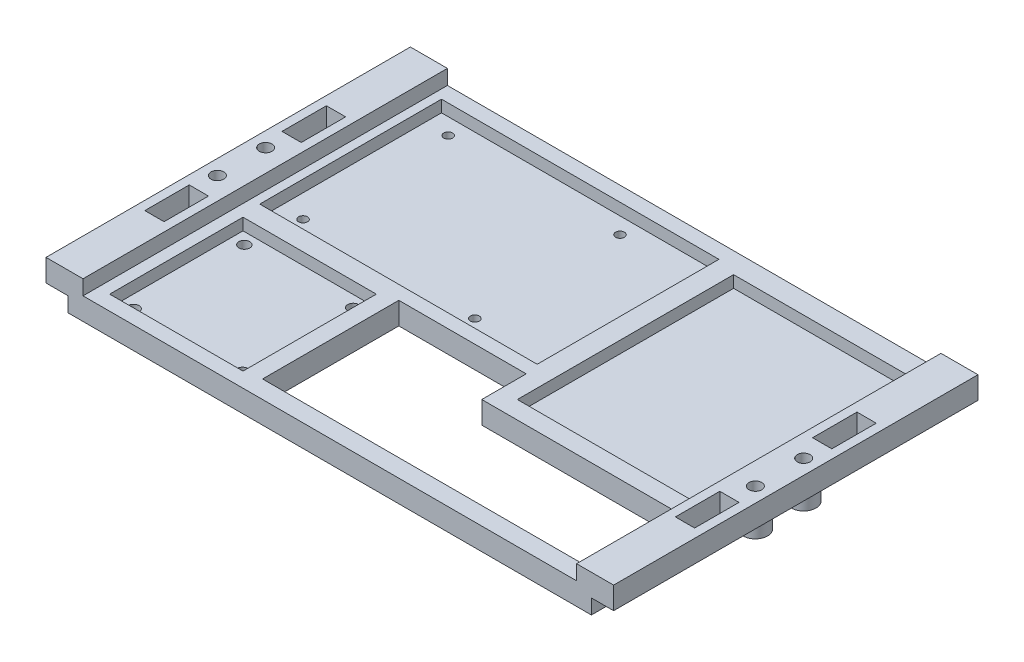
SolidWorks part; units mm, degrees
ref_plane "Front Plane" through (0, 0, 0) normal (0, 0, 1) x (1, 0, 0)
ref_plane "Top Plane" through (0, 0, 0) normal (0, 1, 0) x (1, 0, 0)
ref_plane "Right Plane" through (0, 0, 0) normal (1, 0, 0) x (0, 0, -1)
sketch "Sketch2" plane through (0, 0, 0) normal (0, 0, 1) x (1, 0, 0)
  line L0 (179.1, 12.5) -> (191.6, 12.5)
  line L1 (7.5, 0) -> (184.1, 0)
  line L2 (0, 5) -> (0, 12.5)
  line L3 (0, 12.5) -> (12.5, 12.5)
  line L4 (191.6, 5) -> (191.6, 12.5)
  line L7 (0, 5) -> (7.5, 5)
  line L8 (7.5, 0) -> (7.5, 5)
  line L11 (191.6, 5) -> (184.1, 5)
  line L12 (184.1, 0) -> (184.1, 5)
  line L14 (12.5, 12.5) -> (12.5, 7.5)
  line L15 (12.5, 7.5) -> (179.1, 7.5)
  line L16 (179.1, 12.5) -> (179.1, 7.5)
  dimension "D1" = 191.6
  dimension "D2" = 5
  dimension "D3" = 5
  dimension "D4" = 5
  dimension "D5" = 12.5
  dimension "D6" = 7.5
  dimension "D7" = 7.5
  dimension "D8" = 12.5
  dimension "D9" = 12.5
extrude "PlateFrame" add sketch "Sketch2" along normal blind 150
sketch "Sketch3" plane through (0, 12.5, 0) normal (0, 1, 0) x (1, 0, 0)
  line L0 (12.5, 0) -> (0, 0) construction
  line L2 (0, -150) -> (0, 0) construction
  line L3 (191.6, -150) -> (191.6, 0) construction
  line L4 (191.6, 0) -> (179.1, 0) construction
  circle A0 centre (5, -66.85) radius 2.15
  circle A1 centre (5, -83.15) radius 2.15
  circle A2 centre (186.6, -66.85) radius 2.15
  circle A3 centre (186.6, -83.15) radius 2.15
  dimension "D1" = 4.3
  dimension "D2" = 4.3
  dimension "D3" = 4.3
  dimension "D4" = 4.3
  dimension "D5" = 66.85
  dimension "D6" = 16.3
  dimension "D7" = 5
  dimension "D8" = 5
  dimension "D9" = 5
  dimension "D10" = 181.6
  dimension "D11" = 66.85
  dimension "D12" = 16.3
extrude "HoleSupport" cut sketch "Sketch3" against normal blind 7.5
sketch "Sketch4" plane through (0, 12.5, 0) normal (0, 1, 0) x (1, 0, 0)
  circle A0 centre (5, -66.85) radius 2.15
  circle A1 centre (5, -83.15) radius 2.15
  circle A2 centre (186.6, -83.15) radius 2.15
  circle A3 centre (186.6, -66.85) radius 2.15
  circle A4 centre (186.6, -66.85) radius 4.15
  circle A5 centre (186.6, -83.15) radius 4.15
  circle A6 centre (5, -66.85) radius 4.15
  circle A7 centre (5, -83.15) radius 4.15
  dimension "D1" = 2
extrude "CylindricalSupports" add sketch "Sketch4" against normal blind 12.5
sketch "Sketch5" plane through (0, 7.5, 0) normal (0, 1, 0) x (1, 0, 0)
  line L0 (12.5, -150) -> (12.5, 0) construction
  line L1 (17.5, -87) -> (60.5, -87)
  line L2 (12.5, -150) -> (12.5, 0) construction
  line L3 (17.5, -20) -> (107.15, -20)
  line L4 (17.5, -20) -> (17.5, -77.35)
  line L5 (17.5, -77.35) -> (107.15, -77.35)
  line L6 (107.15, -20) -> (107.15, -77.35)
  line L7 (174.1, -20) -> (116.1, -20)
  line L8 (174.1, -20) -> (174.1, -93)
  line L9 (174.1, -93) -> (116.1, -93)
  line L10 (116.1, -20) -> (116.1, -93)
  line L15 (179.1, -150) -> (179.1, 0) construction
  line L16 (179.1, 0) -> (12.5, 0) construction
  line L17 (17.5, -87) -> (17.5, -130)
  line L18 (17.5, -130) -> (60.5, -130)
  line L19 (60.5, -87) -> (60.5, -130)
  line L20 (179.1, -150) -> (12.5, -150) construction
  dimension "D1" = 5
  dimension "D2" = 89.65
  dimension "D3" = 57.35
  dimension "D4" = 5
  dimension "D5" = 43
  dimension "D6" = 58
  dimension "D7" = 43
  dimension "D8" = 20
  dimension "D9" = 20
  dimension "D10" = 5
  dimension "D11" = 73
  dimension "D12" = 20
extrude "ItemLayout" cut sketch "Sketch5" against normal blind 4
sketch "Sketch6" plane through (0, 7.5, 0) normal (0, 1, 0) x (1, 0, 0)
  line L1 (67.1, -84) -> (110.1, -84)
  line L2 (67.1, -84) -> (67.1, -130)
  line L3 (67.1, -130) -> (110.1, -130)
  line L4 (110.1, -84) -> (110.1, -99)
  line L9 (179.1, -150) -> (179.1, 0) construction
  line L10 (110.1, -130) -> (174.1, -130)
  line L12 (110.1, -99) -> (174.1, -99)
  line L13 (174.1, -130) -> (174.1, -99)
  line L14 (116.1, -93) -> (174.1, -93) construction
  line L15 (116.1, -20) -> (116.1, -93) construction
  line L17 (179.1, -150) -> (12.5, -150) construction
  dimension "D1" = 20
  dimension "D2" = 43
  dimension "D3" = 5
  dimension "D4" = 6
  dimension "D5" = 6
  dimension "D6" = 15
extrude "HoleCutout" cut sketch "Sketch6" against normal blind 7.5
sketch "Sketch7" plane through (0, 3.5, 0) normal (0, 1, 0) x (1, 0, 0)
  line L0 (17.5, -20) -> (17.5, -77.35) construction
  line L1 (17.5, -20) -> (17.5, -77.35) construction
  line L2 (107.15, -20) -> (17.5, -20) construction
  line L3 (107.15, -20) -> (17.5, -20) construction
  circle A0 centre (23.26, -23.5) radius 1.5
  circle A1 centre (23.26, -72.5) radius 1.5
  circle A2 centre (81.26, -72.5) radius 1.5
  circle A3 centre (81.26, -23.5) radius 1.5
  dimension "D1" = 3
  dimension "D2" = 3
  dimension "D3" = 3
  dimension "D4" = 3
  dimension "D5" = 5.76
  dimension "D6" = 5.76
  dimension "D7" = 3.5
  dimension "D8" = 3.5
  dimension "D9" = 58
  dimension "D10" = 58
  dimension "D11" = 49
  dimension "D12" = 49
extrude "HoleRaspberryPi" cut sketch "Sketch7" against normal blind 3.5
sketch "Sketch8" plane through (0, 3.5, 0) normal (0, 1, 0) x (1, 0, 0)
  line L0 (17.5, -130) -> (60.5, -130) construction
  line L1 (60.5, -87) -> (17.5, -87) construction
  line L2 (60.5, -130) -> (60.5, -87) construction
  line L3 (60.5, -130) -> (60.5, -87) construction
  line L4 (17.5, -87) -> (17.5, -130) construction
  line L5 (17.5, -130) -> (60.5, -130) construction
  circle A0 centre (57.56, -127.24) radius 1.85
  circle A1 centre (57.56, -89.86) radius 1.85
  circle A2 centre (20.81, -89.86) radius 1.85
  circle A3 centre (20.81, -127.24) radius 1.85
  dimension "D1" = 3.7
  dimension "D2" = 3.7
  dimension "D3" = 3.7
  dimension "D4" = 3.7
  dimension "D6" = 2.86
  dimension "D8" = 2.94
  dimension "D9" = 2.86
  dimension "D10" = 3.31
  dimension "D11" = 2.76
  dimension "D12" = 3.31
  dimension "D5" = 2.76
  dimension "D7" = 2.94
extrude "HoleMotorDriver" cut sketch "Sketch8" against normal blind 3.5
sketch "Sketch10" plane through (0, 7.5, 0) normal (0, 1, 0) x (1, 0, 0)
  line L1 (17.5, -87) -> (60.5, -87)
  line L2 (17.5, -87) -> (17.5, -130)
  line L3 (17.5, -130) -> (60.5, -130)
  line L4 (60.5, -87) -> (60.5, -130)
  line L5 (16.5, -86) -> (61.5, -86)
  line L6 (16.5, -86) -> (16.5, -131)
  line L7 (16.5, -131) -> (61.5, -131)
  line L8 (61.5, -86) -> (61.5, -131)
  dimension "D1" = 1
  dimension "D2" = 1
  dimension "D3" = 1
  dimension "D4" = 1
extrude "CutMotorDriver" cut sketch "Sketch10" against normal blind 4
sketch "Sketch11" plane through (0, 7.5, 0) normal (0, 1, 0) x (1, 0, 0)
  line L1 (17.5, -20) -> (107.15, -20)
  line L2 (17.5, -20) -> (17.5, -77.35)
  line L3 (17.5, -77.35) -> (107.15, -77.35)
  line L4 (107.15, -20) -> (107.15, -77.35)
  line L5 (109.15, -79.35) -> (15.5, -79.35)
  line L6 (109.15, -79.35) -> (109.15, -18)
  line L7 (109.15, -18) -> (15.5, -18)
  line L8 (15.5, -79.35) -> (15.5, -18)
  dimension "D1" = 2
  dimension "D2" = 2
  dimension "D3" = 2
  dimension "D4" = 2
extrude "CutPaspberryPi" cut sketch "Sketch11" against normal blind 4
sketch "Sketch12" plane through (0, 12.5, 0) normal (0, 1, 0) x (1, 0, 0)
  line L0 (191.6, -150) -> (191.6, 0) construction
  line L1 (0, 0) -> (191.6, 0)
  line L2 (0, 0) -> (0, -13)
  line L3 (0, -13) -> (191.6, -13)
  line L4 (191.6, 0) -> (191.6, -13)
  line L6 (0, -150) -> (191.6, -150)
  line L7 (0, -150) -> (0, -136)
  line L8 (0, -136) -> (191.6, -136)
  line L9 (191.6, -150) -> (191.6, -136)
  line L14 (12.5, -150) -> (0, -150) construction
  circle A0 centre (5, -66.85) radius 2.15 construction
  circle A1 centre (5, -83.15) radius 2.15 construction
  dimension "D1" = 13
  dimension "D2" = 14
extrude "CutPlateEdges" cut sketch "Sketch12" against normal blind 12.5
sketch "Sketch13" plane through (0, 12.5, 0) normal (0, 1, 0) x (1, 0, 0)
  line L0 (12.5, -136) -> (12.5, -13) construction
  line L1 (9.5, -59.35) -> (3, -59.35)
  line L2 (9.5, -59.35) -> (9.5, -44.35)
  line L3 (9.5, -44.35) -> (3, -44.35)
  line L4 (3, -59.35) -> (3, -44.35)
  line L5 (3, -90.65) -> (9.5, -90.65)
  line L6 (3, -90.65) -> (3, -105.65)
  line L7 (3, -105.65) -> (9.5, -105.65)
  line L8 (9.5, -90.65) -> (9.5, -105.65)
  line L9 (182.1, -59.35) -> (188.6, -59.35)
  line L10 (182.1, -59.35) -> (182.1, -44.35)
  line L11 (182.1, -44.35) -> (188.6, -44.35)
  line L12 (188.6, -59.35) -> (188.6, -44.35)
  line L13 (182.1, -90.65) -> (188.6, -90.65)
  line L14 (182.1, -90.65) -> (182.1, -105.65)
  line L15 (182.1, -105.65) -> (188.6, -105.65)
  line L16 (188.6, -90.65) -> (188.6, -105.65)
  line L18 (179.1, -136) -> (179.1, -13) construction
  line L19 (179.1, -136) -> (179.1, -13) construction
  circle A0 centre (5, -66.85) radius 2.15 construction
  circle A1 centre (5, -83.15) radius 2.15 construction
  circle A2 centre (186.6, -66.85) radius 2.15 construction
  circle A3 centre (186.6, -83.15) radius 2.15 construction
  dimension "D1" = 7.5
  dimension "D2" = 7.5
  dimension "D9" = 7.5
  dimension "D3" = 3
  dimension "D4" = 6.5
  dimension "D5" = 15
  dimension "D6" = 3
  dimension "D7" = 6.5
  dimension "D8" = 15
  dimension "D10" = 7.5
  dimension "D11" = 3
  dimension "D12" = 3
  dimension "D13" = 6.5
  dimension "D14" = 6.5
  dimension "D15" = 15
  dimension "D16" = 15
extrude "CutShellHoles" cut sketch "Sketch13" against normal blind 12.5
